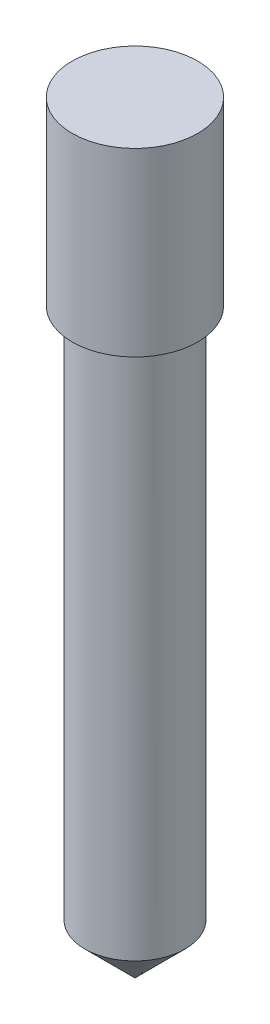
SolidWorks part; units mm, degrees
ref_plane "Front Plane" through (0, 0, 0) normal (0, 0, 1) x (1, 0, 0)
ref_plane "Top Plane" through (0, 0, 0) normal (0, 1, 0) x (1, 0, 0)
ref_plane "Right Plane" through (0, 0, 0) normal (1, 0, 0) x (0, 0, -1)
sketch "Sketch1" plane through (0, 0, 0) normal (0, 1, 0) x (1, 0, 0)
  circle A0 centre (0, 0) radius 5
  dimension "D1" = 10
extrude "Boss-Extrude1" add sketch "Sketch1" along normal blind 58
chamfer "Chamfer1" distance 5 angle 45 1 edges at (0, 0, 5)
sketch "Sketch2" plane through (0, 58, 0) normal (0, 1, 0) x (1, 0, 0)
  circle A1 centre (0, 0) radius 6.25
  point P5 (0, -4.85)
  dimension "D1" = 12.5
extrude "Boss-Extrude2" add sketch "Sketch2" along normal blind 18
